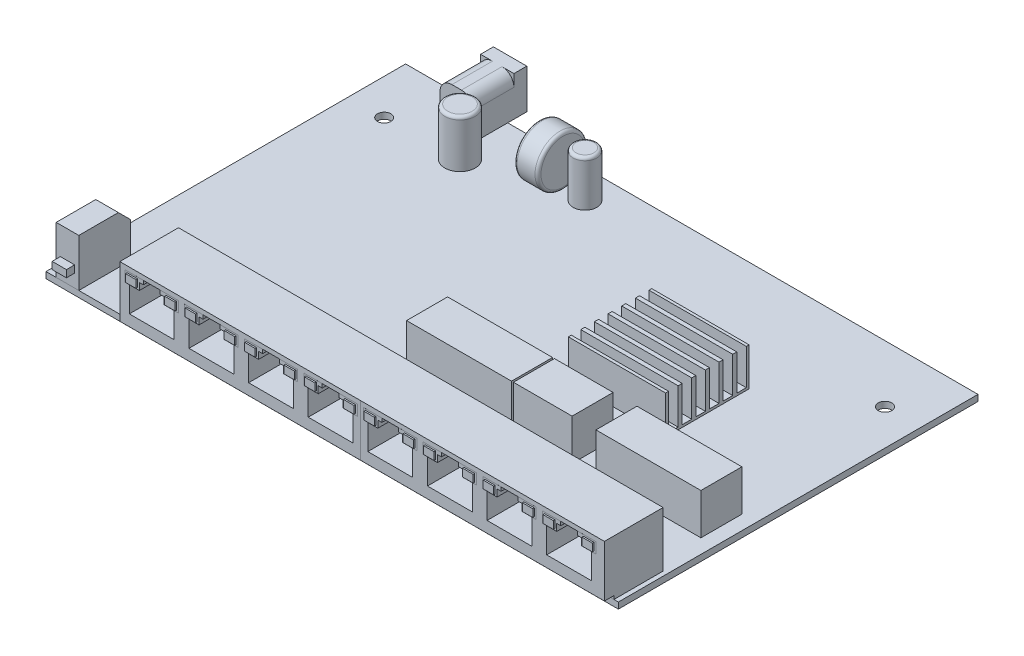
SolidWorks part; units mm, degrees
ref_plane "Front Plane" through (0, 0, 0) normal (0, 0, 1) x (1, 0, 0)
ref_plane "Top Plane" through (0, 0, 0) normal (0, 1, 0) x (1, 0, 0)
ref_plane "Right Plane" through (0, 0, 0) normal (1, 0, 0) x (0, 0, -1)
sketch "Sketch1" plane through (0, 0, 0) normal (0, 1, 0) x (1, 0, 0)
  line L1 (0, 0) -> (152.4, 0)
  line L2 (0, 0) -> (0, -95.758)
  line L3 (0, -95.758) -> (152.4, -95.758)
  line L4 (152.4, 0) -> (152.4, -95.758)
  dimension "D1" = 152.4
  dimension "D2" = 95.758
extrude "Extrude1" add sketch "Sketch1" along normal blind 1.651
sketch "Sketch2" plane through (0, 1.651, 0) normal (0, 1, 0) x (1, 0, 0)
  line L0 (0, -95.758) -> (152.4, -95.758) construction
  line L1 (2.712, -95.758) -> (8.7318, -95.758)
  line L2 (2.712, -95.758) -> (2.712, -82.042)
  line L3 (2.712, -82.042) -> (8.7318, -82.042)
  line L4 (8.7318, -95.758) -> (8.7318, -82.042)
  line L5 (0, 0) -> (0, -95.758) construction
  dimension "D1" = 6.0198
  dimension "D2" = 13.716
  dimension "D3" = 2.712
extrude "Extrude2" add sketch "Sketch2" along normal blind 12.7 separate body
chamfer "Chamfer1" distance 3.175 angle 45 1 edges at (5.7219, 14.351, 82.042)
sketch "Sketch3" plane through (0, 0, 95.758) normal (0, 0, 1) x (1, 0, 0)
  line L0 (2.712, 1.651) -> (8.7318, 1.651) construction
  line L1 (3.8169, 7.006) -> (7.6269, 7.006)
  line L2 (3.8169, 7.006) -> (3.8169, 5.101)
  line L3 (3.8169, 5.101) -> (7.6269, 5.101)
  line L4 (7.6269, 7.006) -> (7.6269, 5.101)
  line L5 (5.7219, 1.651) -> (5.7219, 5.101) construction
  dimension "D1" = 3.81
  dimension "D2" = 1.905
  dimension "D3" = 3.45
extrude "Extrude3" add sketch "Sketch3" along normal blind 2.1844
sketch "Sketch4" plane through (0, 1.651, 0) normal (0, 1, 0) x (1, 0, 0)
  line L1 (22.197, -82.677) -> (151.229, -82.677)
  line L2 (22.197, -82.677) -> (22.197, -98.298)
  line L3 (22.197, -98.298) -> (151.229, -98.298)
  line L4 (151.229, -82.677) -> (151.229, -98.298)
  line L5 (0, -95.758) -> (152.4, -95.758) construction
  line L7 (0, 0) -> (0, -95.758) construction
  dimension "D1" = 129.032
  dimension "D2" = 22.197
  dimension "D3" = 15.621
  dimension "D4" = 2.54
extrude "Extrude4" add sketch "Sketch4" along normal blind 14.665 separate body
sketch "Sketch6" plane through (0, 0, 98.298) normal (0, 0, 1) x (1, 0, 0)
  line L0 (22.197, 1.651) -> (151.229, 1.651) construction
  line L1 (22.197, 16.316) -> (22.197, 1.651) construction
  line L2 (30.706, 5.521) -> (30.706, 15.1222) construction
  line L4 (28.4708, 14.1062) -> (28.4708, 15.1222)
  line L5 (28.4708, 15.1222) -> (32.9412, 15.1222)
  line L6 (32.9412, 14.1062) -> (32.9412, 15.1222)
  line L7 (28.4708, 14.1062) -> (27.404, 14.1062)
  line L28 (24.737, 12.252) -> (24.737, 5.521)
  line L29 (24.737, 5.521) -> (36.675, 5.521)
  line L30 (36.675, 5.521) -> (36.675, 12.252)
  line L33 (34.008, 14.1062) -> (32.9412, 14.1062)
  line L60 (24.737, 12.252) -> (27.404, 12.252)
  line L61 (27.404, 12.252) -> (27.404, 14.1062)
  line L70 (34.008, 14.1062) -> (34.008, 12.252)
  line L71 (34.008, 12.252) -> (36.675, 12.252)
  dimension "D1" = 3.87
  dimension "D2" = 8.5852
  dimension "D3" = 6.731
  dimension "D4" = 11.938
  dimension "D5" = 6.604
  dimension "D6" = 2.54
  dimension "D7" = 4.4704
  dimension "D8" = 1.016
extrude "Cut-Extrude1" cut sketch "Sketch6" against normal blind 11.43
sketch "Sketch8" plane through (0, 0, 98.298) normal (0, 0, 1) x (1, 0, 0)
  line L0 (28.4708, 15.1222) -> (32.9412, 15.1222) construction
  line L1 (27.404, 12.252) -> (23.594, 12.252)
  line L2 (27.404, 12.252) -> (27.404, 14.1062)
  line L3 (27.404, 15.1222) -> (23.594, 15.1222)
  line L4 (23.594, 12.252) -> (23.594, 15.1222)
  line L5 (34.008, 12.252) -> (37.818, 12.252)
  line L6 (34.008, 12.252) -> (34.008, 14.1062)
  line L7 (34.008, 15.1222) -> (37.818, 15.1222)
  line L8 (37.818, 12.252) -> (37.818, 15.1222)
  line L9 (25.499, 15.1222) -> (25.499, 14.7031) construction
  line L10 (24.102, 14.7031) -> (26.896, 14.7031)
  line L11 (24.102, 14.7031) -> (24.102, 12.6711)
  line L12 (24.102, 12.6711) -> (26.896, 12.6711)
  line L13 (26.896, 14.7031) -> (26.896, 12.6711)
  line L14 (34.516, 14.7031) -> (37.31, 14.7031)
  line L15 (34.516, 14.7031) -> (34.516, 12.6711)
  line L16 (34.516, 12.6711) -> (37.31, 12.6711)
  line L17 (37.31, 14.7031) -> (37.31, 12.6711)
  line L18 (23.594, 13.6871) -> (24.102, 13.6871) construction
  line L19 (35.913, 15.1222) -> (35.913, 14.7031) construction
  line L21 (28.4708, 14.1062) -> (27.404, 14.1062)
  line L22 (28.4708, 14.1062) -> (28.4708, 15.1222)
  line L23 (28.4708, 15.1222) -> (27.404, 15.1222)
  line L25 (32.9412, 14.1062) -> (34.008, 14.1062)
  line L26 (32.9412, 14.1062) -> (32.9412, 15.1222)
  line L27 (32.9412, 15.1222) -> (34.008, 15.1222)
  dimension "D1" = 3.81
  dimension "D2" = 2.794
  dimension "D3" = 2.032
extrude "Extrude5" add sketch "Sketch8" along normal blind 0.3969 contours L13 L10 L11 L12 | L17 L14 L15 L16 region at (25.499, 13.6871, 98.298) region at (35.913, 13.6871, 98.298)
extrude "Extrude13" add sketch "Sketch8<3>" along normal blind 0.0013
sketch "Sketch8<3>" plane through (0, 0, 98.298) normal (0, 0, 1) x (1, 0, 0) same geometry as "Sketch8"
pattern_linear "LPattern2" count 8 spacing 15.875 along (1, 0, 0) of "Cut-Extrude1", "Extrude5", "Extrude13"
sketch "Sketch9" plane through (0, 1.651, 0) normal (0, 1, 0) x (1, 0, 0)
  line L0 (152.4, -95.758) -> (152.4, 0) construction
  line L1 (70.231, -59.055) -> (98.171, -59.055)
  line L2 (70.231, -59.055) -> (70.231, -69.977)
  line L3 (70.231, -69.977) -> (98.171, -69.977)
  line L4 (98.171, -59.055) -> (98.171, -69.977)
  line L5 (98.679, -59.055) -> (114.3, -59.055)
  line L6 (98.679, -59.055) -> (98.679, -69.977)
  line L7 (98.679, -69.977) -> (114.3, -69.977)
  line L8 (114.3, -59.055) -> (114.3, -69.977)
  line L9 (120.65, -59.055) -> (148.59, -59.055)
  line L10 (120.65, -59.055) -> (120.65, -69.977)
  line L11 (120.65, -69.977) -> (148.59, -69.977)
  line L12 (148.59, -59.055) -> (148.59, -69.977)
  line L13 (152.4, 0) -> (0, 0) construction
  dimension "D1" = 27.94
  dimension "D2" = 15.621
  dimension "D3" = 27.94
  dimension "D4" = 10.922
  dimension "D5" = 3.81
  dimension "D6" = 6.35
  dimension "D7" = 0.508
  dimension "D8" = 59.055
extrude "Extrude6" add sketch "Sketch9" along normal blind 10.922 separate body
sketch "Sketch10" plane through (0, 1.651, 0) normal (0, 1, 0) x (1, 0, 0)
  line L0 (152.4, -95.758) -> (152.4, 0) construction
  line L1 (94.742, -29.21) -> (120.65, -29.21)
  line L2 (94.742, -29.21) -> (94.742, -51.435)
  line L3 (94.742, -51.435) -> (120.65, -51.435)
  line L4 (120.65, -29.21) -> (120.65, -51.435)
  line L5 (152.4, 0) -> (0, 0) construction
  dimension "D1" = 25.908
  dimension "D2" = 22.225
  dimension "D3" = 31.75
  dimension "D4" = 29.21
extrude "Extrude7" add sketch "Sketch10" along normal blind 10.16 separate body
sketch "Sketch11" plane through (120.65, 0, 0) normal (1, 0, 0) x (0, 0, -1)
  line L0 (-51.435, 11.811) -> (-29.21, 11.811) construction
  line L1 (-50.6412, 11.811) -> (-48.1012, 11.811)
  line L2 (-50.6412, 11.811) -> (-50.6412, 2.286)
  line L3 (-50.6412, 2.286) -> (-48.1012, 2.286)
  line L4 (-48.1012, 11.811) -> (-48.1012, 2.286)
  line L5 (-51.435, 11.811) -> (-51.435, 1.651) construction
  dimension "D1" = 2.54
  dimension "D2" = 0.7937
  dimension "D3" = 9.525
extrude "Extrude8" cut sketch "Sketch11" against normal up to next (25.908 mm away)
pattern_linear "LPattern1" count 6 spacing 3.6322 along (0, 0, -1) of "Extrude8"
sketch "Sketch12" plane through (0, 1.651, 0) normal (0, 1, 0) x (1, 0, 0)
  line L0 (152.4, 0) -> (0, 0) construction
  line L1 (18.288, 5.08) -> (27.178, 5.08)
  line L2 (18.288, 5.08) -> (18.288, -9.144)
  line L3 (18.288, -9.144) -> (27.178, -9.144)
  line L4 (27.178, 5.08) -> (27.178, -9.144)
  line L5 (0, 0) -> (0, -95.758) construction
  dimension "D1" = 14.224
  dimension "D2" = 8.89
  dimension "D3" = 5.08
  dimension "D4" = 18.288
extrude "Extrude9" add sketch "Sketch12" along normal blind 10.541 separate body
sketch "Sketch14" plane through (0, 0, 9.144) normal (0, 0, 1) x (1, 0, 0)
  line L0 (18.288, 12.192) -> (27.178, 12.192) construction
  line L1 (21.463, 12.192) -> (18.288, 12.192)
  line L4 (18.288, 1.651) -> (27.178, 1.651)
  line L5 (27.178, 1.651) -> (27.178, 12.192)
  line L6 (27.178, 12.192) -> (18.288, 12.192)
  line L7 (18.288, 12.192) -> (18.288, 1.651)
  line L9 (27.178, 9.017) -> (27.178, 12.192)
  line L10 (27.178, 12.192) -> (24.003, 12.192)
  line L11 (18.288, 12.192) -> (18.288, 9.017)
  arc A0 (18.288, 9.017) -> (21.463, 12.192) centre (21.463, 9.017) cw
  arc A1 (24.003, 12.192) -> (27.178, 9.017) centre (24.003, 9.017) cw
  dimension "D2" = 3.175
  dimension "D1" = 0
extrude "Extrude10" cut sketch "Sketch14" against normal offset from surface (10.795 mm away) 3.429 up to face at (22.733, 6.9215, -5.08)
sketch "Sketch15" plane through (0, 0, -5.08) normal (0, 0, -1) x (-1, 0, 0)
  line L0 (-22.733, 1.651) -> (-22.733, 4.826) construction
  line L1 (-27.178, 1.651) -> (-18.288, 1.651) construction
  circle A0 centre (-22.733, 8.001) radius 3.175
  dimension "D2" = 6.35
  dimension "D1" = 3.175
extrude "Extrude11" cut sketch "Sketch15" against normal blind 8.89
sketch "Sketch16" plane through (0, 0, 3.81) normal (0, 0, -1) x (-1, 0, 0)
  circle A0 centre (-22.733, 8.001) radius 0.7937
  dimension "D1" = 1.5875
extrude "Extrude12" add sketch "Sketch16" along normal offset from surface (7.62 mm away) 1.27 up to face at (19.558, 8.001, -5.08)
fillet "Fillet1" radius 0.7937 1 edges at (23.5267, 8.001, -3.81)
hole_wizard "9/64 (0.14063) Diameter Hole1" positions "Sketch18" profile "Sketch17" hole size "9/64" standard "Ansi Inch" end condition through all
sketch "Sketch18" plane through (0, 1.651, 0) normal (0, 1, 0) x (-1, 0, 0)
  line L0 (-152.4, 0) -> (0, 0) construction
  line L1 (-76.2, 0) -> (-76.2, 16.0377) construction
  point P0 (-9.525, 15.24)
  point P2 (-142.875, 15.24)
  dimension "D1" = 133.35
  dimension "D2" = 15.24
sketch "Sketch17" plane through (9.525, 1.651, 15.24) normal (1, 0, 0) x (0, 0, 1)
  line L0 (0, 0) -> (0, 1.651)
  line L1 (0, 1.651) -> (1.786, 1.651)
  line L2 (1.786, 1.651) -> (1.786, 0)
  line L5 (1.786, 0) -> (0, 0)
  line L11 (0, -6.35) -> (0, 107.95) construction
  dimension "Thru Hole Dia." = 3.572
  dimension "Thru Hole Depth" = 1.651
sketch "Sketch19" plane through (0, 1.651, 0) normal (0, 1, 0) x (1, 0, 0)
  line L0 (0, 0) -> (0, -95.758) construction
  line L1 (152.4, 0) -> (0, 0) construction
  circle A0 centre (29.21, -14.732) radius 4.064
  dimension "D1" = 8.128
  dimension "D2" = 29.21
  dimension "D3" = 14.732
extrude "Extrude14" add sketch "Sketch19" along normal blind 12.7 separate body
fillet "Fillet2" radius 0.7937 1 edges at (29.21, 14.351, 18.796)
sketch "Sketch20" plane through (0, 1.651, 0) normal (0, 1, 0) x (1, 0, 0)
  line L0 (0, 0) -> (0, -95.758) construction
  line L1 (152.4, 0) -> (0, 0) construction
  circle A0 centre (55.372, -7.62) radius 3.175
  dimension "D1" = 6.35
  dimension "D2" = 55.372
  dimension "D3" = 7.62
extrude "Extrude15" add sketch "Sketch20" along normal blind 12.192 separate body
fillet "Fillet3" radius 0.7937 1 edges at (55.372, 13.843, 10.795)
ref_plane "Plane1" through (46.99, 0, 0) normal (-1, 0, 0) x (0, 0, 1)
sketch "Sketch21" plane through (46.99, 0, 0) normal (-1, 0, 0) x (0, 0, 1)
  line L0 (0, 1.651) -> (95.758, 1.651) construction
  line L2 (0, 1.651) -> (0, 0) construction
  circle A0 centre (8.255, 8.3185) radius 6.6675
  dimension "D1" = 13.335
  dimension "D2" = 8.255
extrude "Extrude16" add sketch "Sketch21" along normal mid plane 6.35 separate body
fillet "Fillet4" radius 0.7937 2 edges at (50.165, 8.3185, 14.9225) (43.815, 8.3185, 14.9225)
sketch "Sketch22" plane through (0, 0, 98.298) normal (0, 0, 1) x (1, 0, 0)
  line L0 (151.229, 16.316) -> (151.229, 1.651) construction
  line L1 (22.197, 1.651) -> (151.229, 1.651)
  line L2 (22.197, 1.651) -> (22.197, 2.551)
  line L3 (22.197, 2.551) -> (151.229, 2.551)
  line L4 (151.229, 1.651) -> (151.229, 2.551)
  dimension "D1" = 0.9
extrude "Cut-Extrude2" cut sketch "Sketch22" against normal up to surface (2.54 mm away) up to face at (76.2, 0.8255, 95.758)
sketch "Sketch23" plane through (0, 16.316, 0) normal (0, 1, 0) x (1, 0, 0)
  line L0 (84.935, -98.6949) -> (87.602, -98.6949) construction
  line L1 (22.197, -98.298) -> (151.229, -98.298) construction
  line L2 (86.2185, -99.1918) -> (86.3185, -99.1918)
  line L3 (86.2185, -99.1918) -> (86.2185, -98.198)
  line L4 (86.2185, -98.198) -> (86.3185, -98.198)
  line L5 (86.3185, -99.1918) -> (86.3185, -98.198)
  line L6 (86.2185, -99.1918) -> (86.3185, -98.198) construction
  line L7 (86.2185, -98.198) -> (86.3185, -99.1918) construction
  point P4 (86.2685, -98.6949)
  dimension "D1" = 0.1
  dimension "D2" = 0.1
extrude "Cut-Extrude3" cut sketch "Sketch23" against normal through all
